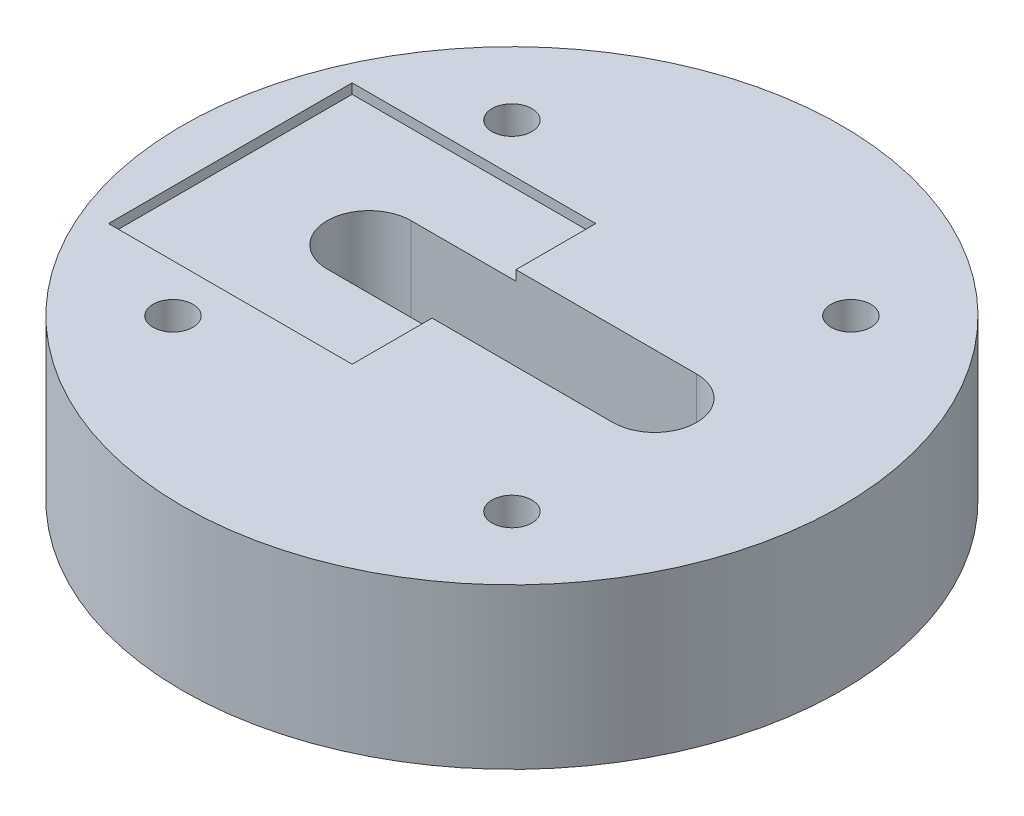
SolidWorks part; units mm, degrees
ref_plane "前视基准面" through (0, 0, 0) normal (0, 0, 1) x (1, 0, 0)
ref_plane "上视基准面" through (0, 0, 0) normal (0, 1, 0) x (1, 0, 0)
ref_plane "右视基准面" through (0, 0, 0) normal (1, 0, 0) x (0, 0, -1)
other "Configuration Table"
sketch "草图1" plane through (0, 0, 0) normal (0, 1, 0) x (1, 0, 0)
  circle A0 centre (0, 0) radius 16.5
  circle A1 centre (0, 0) radius 15.5
  dimension "D1" = 33
  dimension "D2" = 31
extrude "凸台-拉伸1" add sketch "草图1" along normal blind 8 contours A0
extrude "凸台-拉伸2" add sketch "草图1<5>" along normal blind 6 contours A0 | A1
sketch "草图1<5>" plane through (0, 0, 0) normal (0, 1, 0) x (1, 0, 0) same geometry as "草图1"
sketch "草图2" plane through (0, 8, 0) normal (0, 1, 0) x (1, 0, 0)
  line L1 (4.25, 2.1) -> (-4.25, 2.1)
  line L2 (4.25, 2.1) -> (4.25, -2.1)
  line L3 (4.25, -2.1) -> (-4.25, -2.1)
  line L4 (-4.25, 2.1) -> (-4.25, -2.1)
  line L5 (4.25, 2.1) -> (-4.25, -2.1) construction
  line L6 (4.25, -2.1) -> (-4.25, 2.1) construction
  circle A0 centre (4.25, 0) radius 2.1
  circle A1 centre (-4.25, 0) radius 2.1
  dimension "D1" = 4.2
  dimension "D2" = 8.5
extrude "切除-拉伸1" cut sketch "草图2" against normal through all contours L4 A1 | L2 A0 | L1 L4 L3 L2 region at (5.1413, 8, 0) region at (-5.1413, 8, 0)
sketch "草图3" plane through (0, 8, 0) normal (0, 1, 0) x (1, 0, 0)
  line L1 (-7.15, -2.1) -> (7.15, -2.1)
  line L2 (-7.15, -2.1) -> (-7.15, 2.1)
  line L3 (-7.15, 2.1) -> (7.15, 2.1)
  line L4 (7.15, -2.1) -> (7.15, 2.1)
  line L5 (-7.15, -2.1) -> (7.15, 2.1) construction
  line L6 (-7.15, 2.1) -> (7.15, -2.1) construction
  circle A0 centre (-7.15, 0) radius 2.1
  circle A1 centre (7.15, 0) radius 2.1
  point P0 (0, 0)
  dimension "D1" = 4.2
  dimension "D2" = 14.3
extrude "切除-拉伸2" cut sketch "草图3" against normal offset from surface (6 mm away) 2 contours L2 A0 | L4 A1 | L3 L4 L1 L2 region at (-8.0413, 8, 0) region at (8.0413, 8, 0) up to face at (0, 0, 16.5)
sketch "草图4" plane through (0, 2, 0) normal (0, 1, 0) x (1, 0, 0)
  circle A0 centre (-7.7, 0) radius 0.4
  circle A1 centre (7.7, 0) radius 0.4
  dimension "D1" = 0.8
extrude "切除-拉伸3" cut sketch "草图4" against normal blind 2
sketch "草图5" plane through (0, 8, 0) normal (0, 1, 0) x (1, 0, 0)
  line L0 (5.1, 0) -> (0, 0) construction
  line L1 (-1.9, 6.1) -> (-14.1, 6.1)
  line L2 (-1.9, 6.1) -> (-1.9, -6.1)
  line L3 (-1.9, -6.1) -> (-14.1, -6.1)
  line L4 (-14.1, 6.1) -> (-14.1, -6.1)
  line L5 (5.1, 1.6) -> (-1.9, 1.6)
  line L6 (5.1, 1.6) -> (5.1, -1.6)
  line L7 (5.1, -1.6) -> (-1.9, -1.6)
  line L8 (-1.9, 1.6) -> (-1.9, -1.6)
  line L9 (0, 0) -> (-8, 0) construction
  line L10 (-8, 6.1) -> (-8, -6.1) construction
  dimension "D1" = 12.2
  dimension "D2" = 7
  dimension "D3" = 3.2
  dimension "D4" = 8
extrude "切除-拉伸4" cut sketch "草图5" against normal blind 0.5 contours L3 L4 L1 L2 | L7 L8 L5 L6
sketch "草图6" plane through (0, 0, 0) normal (0, -1, 0) x (1, 0, 0)
  line L0 (0, 0) -> (0, 23.2306)
  line L1 (8.4853, 8.4853) -> (0, 0)
  circle A0 centre (8.4853, 8.4853) radius 1.5
  circle A1 centre (8.4853, 8.4853) radius 1
  dimension "D2" = 3
  dimension "D3" = 2
  dimension "D1" = 45
  dimension "D4" = 12
extrude "切除-拉伸5" cut sketch "草图6" against normal through all contours A1
extrude "切除-拉伸6" cut sketch "草图6<3>" against normal offset from surface (6 mm away) 2 contours A0 up to face at (8.4853, 8, 7.4853)
sketch "草图6<3>" plane through (0, 0, 0) normal (0, -1, 0) x (1, 0, 0) same geometry as "草图6"
pattern_circular "阵列(圆周)1" count 4 over 360 about axis through (0, 8, 0) along (0, -1, 0) of "切除-拉伸5", "切除-拉伸6"
